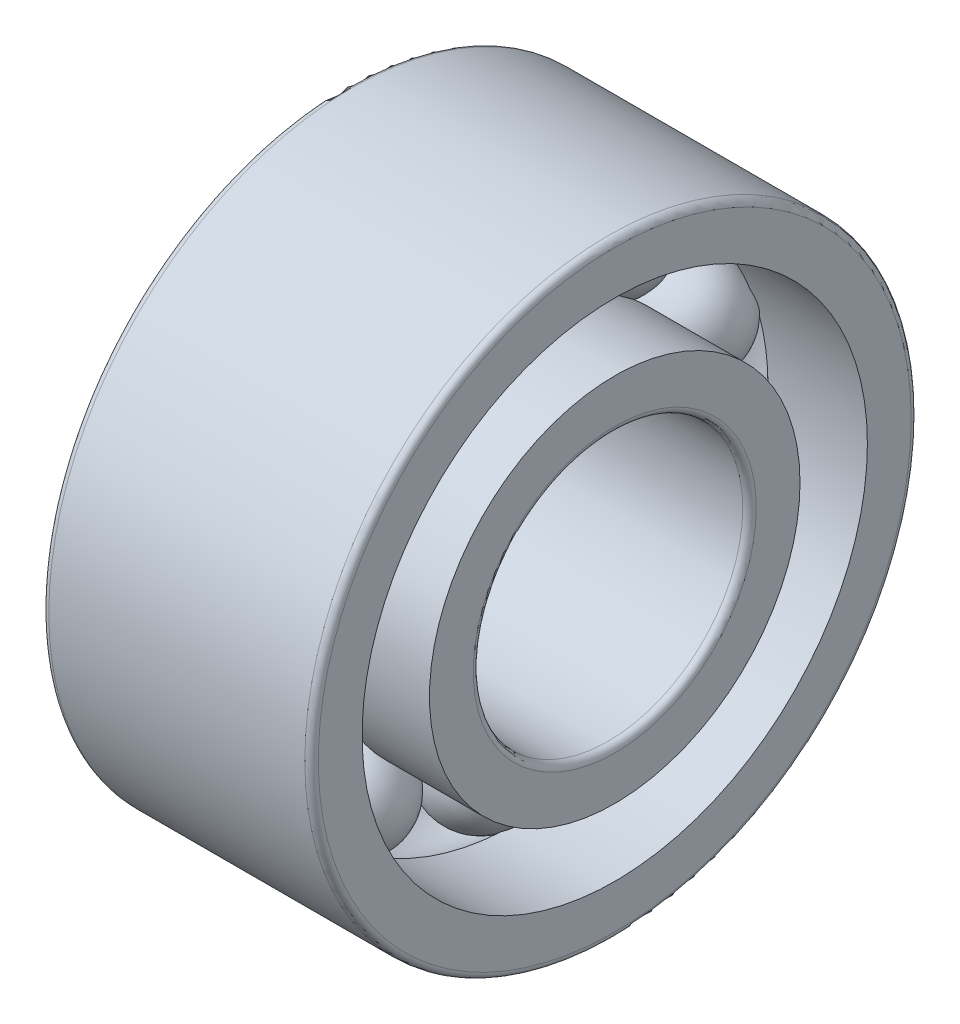
SolidWorks part; units mm, degrees
ref_plane "Plane1" through (0, 0, 0) normal (0, 0, 1) x (1, 0, 0)
ref_plane "Plane2" through (0, 0, 0) normal (0, 1, 0) x (1, 0, 0)
ref_plane "Plane3" through (0, 0, 0) normal (1, 0, 0) x (0, 0, -1)
other "Configuration Table"
sketch "Clipboard" plane through (0, 0, 0) normal (0, 0, 1) x (1, 0, 0)
  line L0 (-10, 0) -> (10, 0) construction
  line L1 (0, 0) -> (22.021, -3.8829)
  line L2 (0, 0) -> (3.2006, 0.5644)
  line L3 (0, 0) -> (22.021, -3.8829)
  line L4 (0, 0) -> (-22.3573, -0.3902)
sketch "CagSpiSke" plane through (0, 0, 0) normal (0, 0, 1) x (1, 0, 0)
  line L0 (0.075, 3.125) -> (0.075, 3.375)
  line L1 (0.075, 3.375) -> (-0.075, 3.375)
  line L2 (-0.075, 3.375) -> (-0.075, 3.125)
  line L3 (-0.075, 3.125) -> (0.075, 3.125)
  line L4 (-20.6375, 0) -> (20.6375, 0) construction
  line L5 (0, 0) -> (0, 23.7692) construction
revolve "CageSpine" add sketch "CagSpiSke" angle 0.001 about L4 reverse direction yes
ref_axis "Axis1" through (-50, 0, 0) along (1, 0, 0)
sketch "CagBalSke" plane through (0, 0, 0) normal (0, 0, 1) x (1, 0, 0)
  line L0 (-0.825, 3.25) -> (0.825, 3.25)
  line L1 (-1.905, 3.25) -> (1.905, 3.25) construction
  line L2 (-10, 0) -> (10, 0) construction
  line L3 (0, 0) -> (0, 24) construction
  arc A0 (0.825, 3.25) -> (-0.825, 3.25) centre (0, 3.25) cw
revolve "CageBall" [suppressed] add sketch "CagBalSke" angle 360 about L1 reverse direction yes
pattern_circular "CageBalls" [suppressed] count 10 every 36 about axis through (-50, 0, 0) along (1, 0, 0)
sketch "CagTrmODSke" plane through (0, 0, 0) normal (0, 0, 1) x (1, 0, 0)
  line L0 (0.826, 3.375) -> (0.826, 4.076)
  line L1 (0.826, 4.076) -> (-0.826, 4.076)
  line L2 (-0.826, 4.076) -> (-0.826, 3.375)
  line L3 (-0.826, 3.375) -> (0.826, 3.375)
  line L4 (-20.6375, 0) -> (20.6375, 0) construction
  line L5 (0, 0) -> (0, 25) construction
revolve "CageTrimOD" [suppressed] cut sketch "CagTrmODSke" angle 360 about L4 reverse direction yes
sketch "CagTrmIDSke" plane through (0, 0, 0) normal (0, 0, 1) x (1, 0, 0)
  line L0 (0.826, 2.426) -> (0.826, 3.125)
  line L1 (0.826, 3.125) -> (-0.826, 3.125)
  line L2 (-0.826, 3.125) -> (-0.826, 2.426)
  line L3 (-0.826, 2.426) -> (0.826, 2.426)
  line L4 (-20.6375, 0) -> (20.6375, 0) construction
  line L5 (0, 0) -> (0, 25) construction
revolve "CageTrimID" [suppressed] cut sketch "CagTrmIDSke" angle 360 about L4 reverse direction yes
sketch "BalSimSke" plane through (0, 0, 0) normal (0, 0, 1) x (1, 0, 0)
  line L0 (-10, 0) -> (10, 0) construction
  line L1 (-10, 3.25) -> (10, 3.25) construction
  line L2 (0, 0) -> (0, 23) construction
  circle A0 centre (0, 3.25) radius 0.75
revolve "BallsSimplified" [suppressed] add sketch "BalSimSke" angle 360 about L0
sketch "BalDetSke" plane through (0, 0, 0) normal (0, 0, 1) x (1, 0, 0)
  line L0 (-0.75, 3.25) -> (0.75, 3.25)
  line L1 (-1.905, 3.25) -> (1.905, 3.25) construction
  line L2 (0, 0) -> (0, 25) construction
  arc A0 (0.75, 3.25) -> (-0.75, 3.25) centre (0, 3.25) cw
revolve "BallDetailed" add sketch "BalDetSke" angle 360 about L1 reverse direction yes
sketch "InnRacSke" plane through (0, 0, 0) normal (0, 0, 1) x (1, 0, 0)
  line L0 (-0.525, 2.75) -> (-2, 2.75)
  line L1 (-2, 2.75) -> (-2, 2.1)
  line L2 (-1.9, 2) -> (1.9, 2)
  line L3 (2, 2.1) -> (2, 2.75)
  line L4 (2, 2.75) -> (0.525, 2.75)
  line L5 (-20.6375, 0) -> (20.6375, 0) construction
  line L6 (0, 0) -> (0, 30) construction
  arc A0 (-2, 2.1) -> (-1.9, 2) centre (-1.9, 2.1) ccw
  arc A1 (1.9, 2) -> (2, 2.1) centre (1.9, 2.1) ccw
  arc A2 (0.525, 2.75) -> (-0.525, 2.75) centre (0, 3.25) cw
  dimension "Width" = 4
revolve "InnerRace" add sketch "InnRacSke" angle 360 about L5 reverse direction yes
sketch "OutRacSke" plane through (0, 0, 0) normal (0, 0, 1) x (1, 0, 0)
  line L0 (-0.525, 3.75) -> (-2, 3.75)
  line L1 (-2, 3.75) -> (-2, 4.4)
  line L2 (-1.9, 4.5) -> (1.9, 4.5)
  line L3 (2, 4.4) -> (2, 3.75)
  line L4 (2, 3.75) -> (0.525, 3.75)
  line L5 (-20.6375, 0) -> (20.6375, 0) construction
  line L6 (0, 0) -> (0, 30) construction
  arc A0 (-2, 4.4) -> (-1.9, 4.5) centre (-1.9, 4.4) cw
  arc A1 (1.9, 4.5) -> (2, 4.4) centre (1.9, 4.4) cw
  arc A2 (0.525, 3.75) -> (-0.525, 3.75) centre (0, 3.25) ccw
  dimension "Width" = 4
revolve "OuterRace" add sketch "OutRacSke" angle 360 about L5 reverse direction yes
pattern_circular "BallsDetailed" count 10 every 36 about axis through (-50, 0, 0) along (1, 0, 0) of "BallDetailed"
equation "\"BallCLRad@Clipboard\" = ( \"OD@OutRacSke\" + \"ID@InnRacSke\" ) / 4"
equation "\"BallCLRad@BalSimSke\" = \"BallCLRad@Clipboard\""
equation "\"BallCLRad@BalDetSke\" = \"BallCLRad@Clipboard\""
equation "\"BallCLRad@InnRacSke\" = \"BallCLRad@Clipboard\""
equation "\"BallCLRad@OutRacSke\" = \"BallCLRad@Clipboard\""
equation "\"Ball_diameter@InnRacSke\" = \"Ball_diameter@BalDetSke\" - 0.05"
equation "\"Ball_diameter@OutRacSke\" = \"Ball_diameter@BalDetSke\" - 0.05"
equation "\"Ball_diameter@BalSimSke\" = \"Ball_diameter@BalDetSke\""
equation "\"Width@OutRacSke\" = \"Width@InnRacSke\""
equation "\"Fillet_radius@OutRacSke\" = \"Fillet_radius@InnRacSke\""
equation "\"Max_count@Clipboard\" = int( 3.14159265 / atn(( \"Ball_diameter@BalDetSke\" / 2) / sqr( \"BallCLRad@Clipboard\"  *  \"BallCLRad@Clipboard\" - ( \"Ball_diameter@BalDetSke\" / 2) *  ( \"Ball_diameter@BalDetSke\" / 2))))"
equation "\"Max_count@Clipboard\" = ((sgn( \"Max_count@Clipboard\" - \"Count@Clipboard\" )-1)*( \"Max_count@Clipboard\" - \"Count@Clipboard\" ))/-2+ \"Count@Clipboard\""
equation "\"Count@BallsDetailed\" = int( \"Show_count@Clipboard\" ) "
equation "\"Count@BallsDetailed\" = ((sgn( \"Count@BallsDetailed\" - \"Max_count@Clipboard\" )-1)*( \"Count@BallsDetailed\" - \"Max_count@Clipboard\" ))/-2+ \"Max_count@Clipboard\""
equation "\"Count@BallsDetailed\" = ((sgn( \"Count@BallsDetailed\" - \"Min_count@Clipboard\" )+1)*( \"Count@BallsDetailed\" - \"Min_count@Clipboard\"))/2 +\"Min_count@Clipboard\""
equation "\"Angle@BallsDetailed\" = 360.0 / \"Max_count@Clipboard\""
equation "\"BallCLRad@CagBalSke\" = \"BallCLRad@Clipboard\""
equation "\"Count@CageBalls\" = \"Count@BallsDetailed\""
equation "\"Angle@CageBalls\" = \"Angle@BallsDetailed\""
equation "\"Angle@CageSpine\" =  \"Angle@CageBalls\" * ( \"Count@CageBalls\" -1 + int( \"Count@CageBalls\" / \"Max_count@Clipboard\" ) )  + 0.001 -  int( \"Count@CageBalls\" / \"Max_count@Clipboard\" ) * 0.001"
equation "\"Angle@CageSpine\" =  \"Angle@CageSpine\" * int( \"Min_count@Clipboard\" / 2) + int(1 / \"Min_count@Clipboard\")  * 0.001"
equation "\"CageWallOD@CagBalSke\" =  \"Ball_diameter@BalDetSke\" * 1.1"
equation "\"Thickness@CagSpiSke\" =  \"Ball_diameter@BalDetSke\" * 0.1"
equation "\"OD@CagTrmODSke\" = \"BallCLRad@Clipboard\" * 2 + \"CageWallOD@CagBalSke\" + 0.002"
equation "\"ID@CagTrmODSke\" = \"BallCLRad@Clipboard\" * 2 + \"Ball_diameter@BalDetSke\" / 6"
equation "\"OD@CagTrmIDSke\" = \"BallCLRad@Clipboard\" * 2 - \"Ball_diameter@BalDetSke\" / 6"
equation "\"ID@CagTrmIDSke\" = \"BallCLRad@Clipboard\" * 2 - \"CageWallOD@CagBalSke\" + 0.002"
equation "\"OD@CagSpiSke\" = \"ID@CagTrmODSke\""
equation "\"ID@CagSpiSke\" = \"OD@CagTrmIDSke\""
equation "\"Width@CagTrmODSke\" = \"CageWallOD@CagBalSke\" + 0.002"
equation "\"Width@CagTrmIDSke\" = \"CageWallOD@CagBalSke\" + 0.002"
